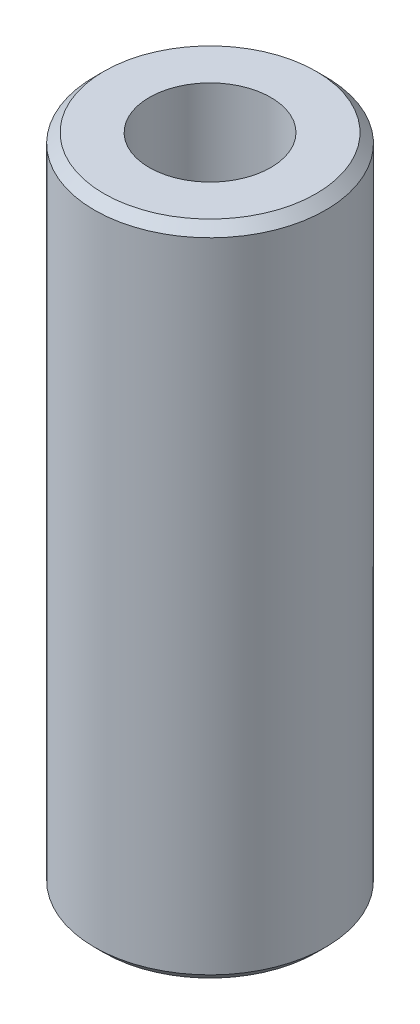
SolidWorks part; units mm, degrees
ref_plane "Front Plane" through (0, 0, 0) normal (0, 0, 1) x (1, 0, 0)
ref_plane "Top Plane" through (0, 0, 0) normal (0, 1, 0) x (1, 0, 0)
ref_plane "Right Plane" through (0, 0, 0) normal (1, 0, 0) x (0, 0, -1)
sketch "Sketch1" plane through (0, 0, 0) normal (0, 1, 0) x (1, 0, 0)
  circle A0 centre (0, 0) radius 47.5
  dimension "SHAFT_OD" = 95
extrude "Boss-Extrude1" add sketch "Sketch1" along normal blind 270.1908
sketch "Sketch2" plane through (0, 0, 0) normal (0, 1, 0) x (1, 0, 0)
  circle A0 centre (0, 0) radius 24.9845
  dimension "BORE_D" = 49.9691
extrude "Cut-Extrude1" cut sketch "Sketch2" along normal through all
chamfer "Chamfer1" distance 3.904 angle 45 2 edges at (0, 270.1908, 47.5) (0, 0, 47.5)
